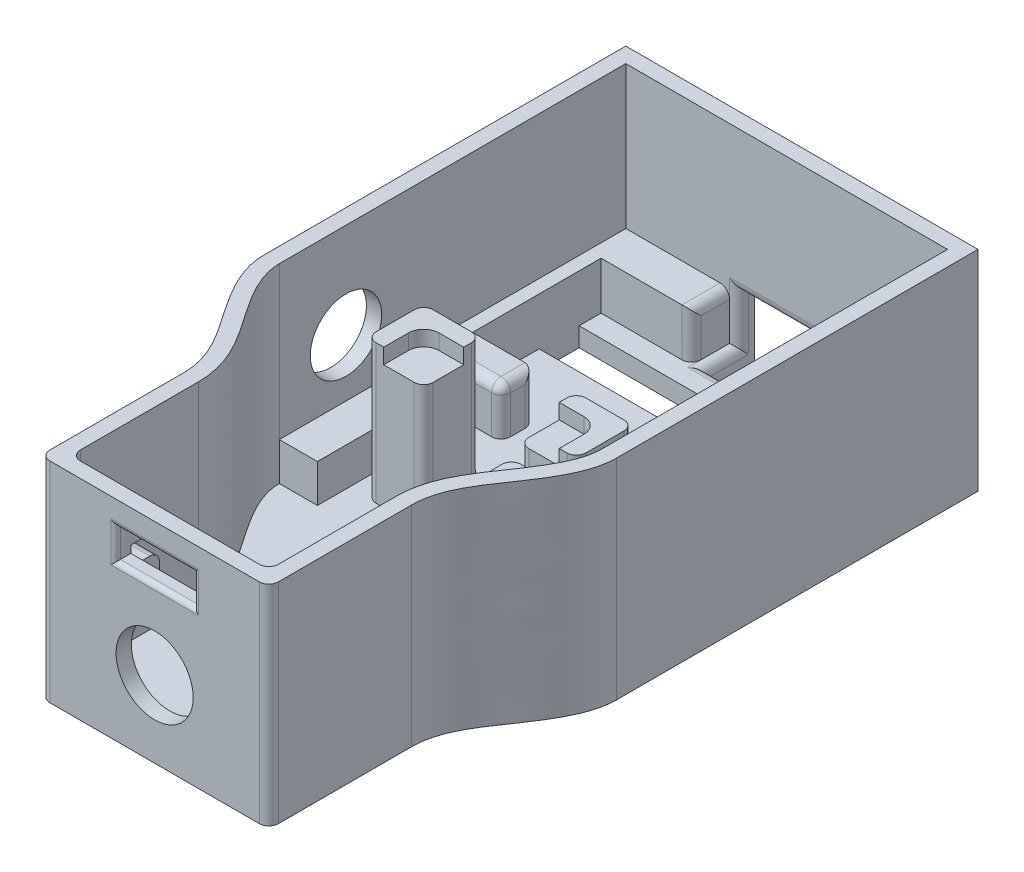
SolidWorks part; units mm, degrees
material "Melamine resin"
ref_plane "Front Plane" through (0, 0, 0) normal (0, 0, 1) x (1, 0, 0)
ref_plane "Top Plane" through (0, 0, 0) normal (0, 1, 0) x (1, 0, 0)
ref_plane "Right Plane" through (0, 0, 0) normal (1, 0, 0) x (0, 0, -1)
sketch "Sketch1" plane through (0, 0, 0) normal (0, 1, 0) x (1, 0, 0)
  line L0 (-18.5, 68) -> (0, 68)
  line L9 (0, 68) -> (0, 0)
  line L10 (-18.5, 68) -> (-18.5, 30)
  line L11 (0, 0) -> (-12, 0)
  line L12 (-12, 0) -> (-12, 15)
  line L13 (-18.5, 30) -> (-12, 30) construction
  line L14 (-12, 30) -> (-12, 15) construction
  line L15 (-15.25, 22.5) -> (-12, 22.5) construction
  line L16 (0, 1.6) -> (-10.4, 1.6)
  line L17 (-15.25, 30) -> (-15.25, 22.5) construction
  line L18 (-10.4, 1.6) -> (-10.4, 15)
  line L19 (-16.9, 66.4) -> (-16.9, 30)
  line L20 (-16.9, 66.4) -> (0, 66.4)
  line L21 (0, 68) -> (0, 66.4)
  line L22 (0, 1.6) -> (0, 0)
  spline S0 degree 3 poles (-18.5, 30) (-18.5, 27.3947) (-15.25, 22.3602) (-12, 17.8849) (-12, 15) knots 0 0 0 0 0.5 1 1 1 1
  spline S1 degree 1 poles (-16.9, 30) (-10.4, 15) knots 0 0 1 1 construction
  spline S2 degree 3 poles (-10.4, 15) (-10.4, 15.4256) (-10.4616, 16.2904) (-10.7983, 17.8861) (-11.54, 19.6983) (-12.6996, 21.6224) (-13.9392, 23.4086) (-15.1181, 25.1604) (-16.1016, 26.879) (-16.6415, 28.2398) (-16.8623, 29.268) (-16.9, 29.7529) (-16.9, 30) knots 0 0 0 0 0.0625 0.125 0.25 0.375 0.5 0.625 0.75 0.875 0.9375 1 1 1 1
  dimension "D1" = 18.5
  dimension "D2" = 68
  dimension "D3" = 15
  dimension "D4" = 15
  dimension "D5" = 12
  dimension "D6" = 1.6
extrude "Boss-Extrude1" add sketch "Sketch1" against normal blind 2 contours S0 L12 L11 L9 L0 L10
extrude "Boss-Extrude2" add sketch "Sketch1<3>" along normal blind 20 contours L18 S2 L19 L20 L9 L0 L10 S0 L12 L11 L16 region at (-9.25, 0, -67.2953)
sketch "Sketch1<3>" plane through (0, 0, 0) normal (0, 1, 0) x (1, 0, 0) same geometry as "Sketch1"
fillet "Fillet1" radius 1 2 edges at (-10.4, 10, -1.6) (-12, 9, 0)
mirror "Mirror1" about plane through (0, 0, 0) normal (1, 0, 0) of "Boss-Extrude2", "Fillet1", "Boss-Extrude1"
sketch "Sketch2" plane through (0, 0, 0) normal (0, 0, 1) x (1, 0, 0)
  line L0 (0, 0) -> (0, 6) construction
  line L1 (0, 6) -> (0, 15.84) construction
  line L2 (4.1, 14.24) -> (-4.1, 14.24)
  line L3 (4.1, 14.24) -> (4.1, 17.44)
  line L4 (4.1, 17.44) -> (-4.1, 17.44)
  line L5 (-4.1, 14.24) -> (-4.1, 17.44)
  line L6 (4.1, 14.24) -> (-4.1, 17.44) construction
  line L7 (4.1, 17.44) -> (-4.1, 14.24) construction
  line L8 (11, 20) -> (-11, 20) construction
  circle A0 centre (0, 6) radius 4.05
  point P4 (0, 15.84)
  dimension "D1" = 8.1
  dimension "D2" = 6
  dimension "D3" = 8.2
  dimension "D4" = 3.2
  dimension "D5" = 4.16
extrude "Cut-Extrude1" cut sketch "Sketch2" against normal up to next
sketch "Sketch3" plane through (0, 0, 0) normal (0, 1, 0) x (1, 0, 0)
  line L0 (-15.5, 55.65) -> (15.5, 55.65) construction
  line L1 (-16.9, 66.4) -> (-6, 66.4)
  line L2 (-16.9, 66.4) -> (-16.9, 45.4)
  line L3 (-16.9, 45.4) -> (-9, 45.4)
  line L4 (16.9, 66.4) -> (16.9, 45.4)
  line L5 (9, 45.4) -> (16.9, 45.4)
  line L7 (-9, 48.9) -> (-9, 45.4)
  line L9 (9, 48.9) -> (9, 45.4)
  line L10 (9, 48.9) -> (15.5, 48.9)
  line L11 (-15.5, 62.4) -> (-6, 62.4)
  line L12 (-15.5, 62.4) -> (-15.5, 48.9)
  line L13 (-15.5, 48.9) -> (-9, 48.9)
  line L14 (15.5, 62.4) -> (15.5, 48.9)
  line L15 (-9, 45.4) -> (9, 45.4) construction
  line L16 (-9, 48.9) -> (9, 48.9) construction
  line L17 (0, 66.4) -> (0, 62.4) construction
  line L18 (0, 62.4) -> (0, 48.9) construction
  line L19 (0, 48.9) -> (0, 45.4) construction
  line L20 (16.9, 66.4) -> (16.9, 30) construction
  line L21 (-6, 62.4) -> (-6, 66.4)
  line L22 (6, 62.4) -> (6, 66.4)
  line L23 (6, 62.4) -> (15.5, 62.4)
  line L24 (6, 66.4) -> (16.9, 66.4)
  line L25 (-6, 66.4) -> (6, 66.4) construction
  line L26 (-16.9, 66.4) -> (16.9, 66.4) construction
  line L27 (-6, 62.4) -> (6, 62.4) construction
  point P23 (0, 55.65)
  dimension "D1" = 31
  dimension "D2" = 13.5
  dimension "D3" = 12
  dimension "D4" = 4
  dimension "D5" = 18
  dimension "D6" = 3.5
extrude "Boss-Extrude3" add sketch "Sketch3" along normal blind 5
ref_plane "IR_mid" through (0, 0, -55.65) normal (0, 0, 1) x (1, 0, 0)
sketch "Sketch4" plane through (0, 0, -68) normal (0, 0, -1) x (-1, 0, 0)
  line L0 (18.5, -2) -> (-18.5, -2) construction
  line L1 (-5, -2) -> (5, -2)
  line L2 (-5, -2) -> (-5, 5)
  line L3 (-5, 5) -> (5, 5)
  line L4 (5, -2) -> (5, 5)
  line L5 (0, 5) -> (0, -2) construction
  dimension "D1" = 10
  dimension "D2" = 7
extrude "Cut-Extrude2" cut sketch "Sketch4" against normal blind 5
sketch "Sketch5" plane through (-18.5, 0, 0) normal (-1, 0, 0) x (0, 0, 1)
  line L0 (-37, 20) -> (-37, 0) construction
  line L1 (-68, 20) -> (-30, 20) construction
  line L2 (-37, 0) -> (0, 0) construction
  circle A0 centre (-37, 10) radius 3.75
  dimension "D1" = 7.5
  dimension "D2" = 37
extrude "Cut-Extrude3" cut sketch "Sketch5" against normal up to next
sketch "Sketch6" plane through (0, 0, 0) normal (0, 1, 0) x (1, 0, 0)
  line L0 (-16.9, 45.4) -> (-16.9, 30) construction
  line L1 (-16.9, 45.4) -> (-12.9, 45.4)
  line L2 (-16.9, 45.4) -> (-16.9, 30)
  line L3 (-16.9, 30) -> (-12.9, 30)
  line L4 (-12.9, 45.4) -> (-12.9, 30)
  spline S0 degree 3 poles (-10.4, 15) (-10.4, 15.4256) (-10.4616, 16.2904) (-10.7983, 17.8861) (-11.54, 19.6983) (-12.6996, 21.6224) (-13.9392, 23.4086) (-15.1181, 25.1604) (-16.1016, 26.879) (-16.6415, 28.2398) (-16.8623, 29.268) (-16.9, 29.7529) (-16.9, 30) knots 0 0 0 0 0.0625 0.125 0.25 0.375 0.5 0.625 0.75 0.875 0.9375 1 1 1 1 construction
  dimension "D1" = 4
extrude "Boss-Extrude4" add sketch "Sketch6" along normal blind 4
sketch "Sketch7" plane through (0, 0, -1.6) normal (0, 0, -1) x (-1, 0, 0)
  line L0 (4.1, 13) -> (9, 13)
  line L1 (11.1, 11) -> (4.1, 11)
  line L4 (4.1, 11) -> (4.1, 13)
  line L5 (9, 13) -> (9, 15)
  line L10 (4.1, 11) -> (0, 11) construction
  line L11 (9, 15) -> (4.1, 15)
  line L12 (-9.4, 0) -> (9.4, 0) construction
  line L13 (0, 0) -> (0, 11) construction
  line L14 (4.1, 15) -> (4.1, 17)
  line L15 (4.1, 17) -> (11.1, 17)
  line L16 (11.1, 11) -> (11.1, 17)
  line L17 (4.1, 13) -> (4.1, 15) construction
  dimension "D1" = 7
  dimension "D2" = 2
  dimension "D3" = 11
  dimension "D4" = 4.1
  dimension "D5" = 2
  dimension "D6" = 9
extrude "Boss-Extrude5" add sketch "Sketch7" along normal blind 3
sketch "Sketch9" plane through (0, 0, 0) normal (0, 1, 0) x (1, 0, 0)
  line L0 (0, 0) -> (0, 36.788) construction
  line L1 (-5.018, 33.288) -> (-11.018, 33.288)
  line L2 (-5.018, 33.288) -> (-5.018, 39.288)
  line L3 (-5.018, 39.288) -> (-11.018, 39.288)
  line L4 (-11.018, 33.288) -> (-11.018, 39.288)
  line L5 (-8.518, 36.788) -> (-8.518, 39.288) construction
  line L6 (-8.518, 36.788) -> (-11.018, 36.788) construction
  line L7 (0, 36.788) -> (-8.518, 36.788) construction
  point P0 (-8.518, 36.788)
  dimension "D1" = 2.5
  dimension "D2" = 2.5
  dimension "D3" = 8.518
  dimension "D4" = 36.788
  dimension "D5" = 6
  dimension "D6" = 6
extrude "Boss-Extrude7" add sketch "Sketch9" along normal up to surface (13 mm away) up to face at (-6.55, 13, -3.1)
sketch "Sketch10" plane through (0, 13, 0) normal (0, 1, 0) x (1, 0, 0)
  line L0 (-11.018, 39.288) -> (-11.018, 33.288)
  line L1 (-11.018, 33.288) -> (-11.018, 39.288) construction
  line L2 (-5.018, 33.288) -> (-11.018, 33.288) construction
  line L3 (-11.018, 33.288) -> (-9.218, 33.288)
  line L4 (-9.218, 33.288) -> (-9.218, 37.488) construction
  line L5 (-9.218, 37.488) -> (-5.018, 37.488) construction
  line L6 (-5.018, 39.288) -> (-5.018, 33.288) construction
  line L7 (-5.018, 37.488) -> (-5.018, 39.288)
  line L8 (-5.018, 39.288) -> (-11.018, 39.288)
  line L10 (-11.018, 39.288) -> (-5.018, 39.288) construction
  line L11 (-5.018, 37.488) -> (-7.618, 37.488)
  line L12 (-9.218, 33.288) -> (-9.218, 35.888)
  arc A0 (-9.218, 35.888) -> (-7.618, 37.488) centre (-7.618, 35.888) cw
  dimension "D2" = 1.6
  dimension "D1" = 1.8
extrude "Boss-Extrude8" add sketch "Sketch10" along normal blind 1.6
mirror "Mirror2" about plane through (0, 0, 0) normal (1, 0, 0) of "Boss-Extrude8", "Boss-Extrude5", "Boss-Extrude7"
sketch "Sketch11" plane through (0, 0, 0) normal (0, 1, 0) x (1, 0, 0)
  line L1 (5, 42.488) -> (-5, 42.488)
  line L2 (5, 42.488) -> (5, 37.488)
  line L3 (5, 37.488) -> (-5, 37.488)
  line L4 (-5, 42.488) -> (-5, 37.488)
  line L5 (5, 42.488) -> (-5, 37.488) construction
  line L6 (5, 37.488) -> (-5, 42.488) construction
  circle A0 centre (0, 39.988) radius 1.25 construction
  point P0 (0, 39.988)
  dimension "D1" = 10
  dimension "D2" = 5
extrude "Boss-Extrude9" add sketch "Sketch11" along normal blind 1.95
fillet "Fillet2" radius 1 28 edges at (-6, 2.5, -62.4) (-9, 2.5, -48.9) (-11.018, 7.3, -33.288) (-11.018, 7.3, -39.288) (-5, 0.975, -42.488) (-9, 2.5, -45.4) (0, 5, -66.4) (5, 2.5, -66.4) (-5, 2.5, -66.4) (-5, 0, -64.7) (5, 0, -64.7) (0, 0, -63) (6, 2.5, -62.4) (9, 2.5, -45.4) (9, 2.5, -48.9) (11.018, 7.3, -33.288) (11.018, 7.3, -39.288) (5, 0.975, -42.488) (5.018, 6.5, -33.288) (-5.018, 6.5, -33.288) (5.018, 7.3, -39.288) (-5.018, 7.3, -39.288) (6, 5, -64.4) (-6, 5, -64.4) (-9, 5, -47.15) (9, 5, -47.15) (-12.95, 5, -45.4) (12.95, 5, -45.4)
sketch "Sketch12" plane through (0, 1.95, 0) normal (0, 1, 0) x (1, 0, 0)
  circle A0 centre (0, 39.988) radius 1.7
  dimension "D1" = 3.4
extrude "Cut-Extrude4" cut sketch "Sketch12" against normal up to next
chamfer "Chamfer1" distance 1.8 angle 45 1 edges at (0, -2, -41.688)
fillet "Fillet3" radius 0.5 1 edges at (0, -0.2, -41.688)
chamfer "Chamfer2" distance 1.95 angle 45 6 edges at (0, 0, -37.488) (-5, 0, -39.488) (-4.7071, 0, -42.1951) (5, 0, -39.488) (4.7071, 0, -42.1951) (0, 0, -42.488)
fillet "Fillet4" radius 0.5 4 edges at (4.1, 15.84, 0) (0, 14.24, 0) (0, 17.44, 0) (-4.1, 15.84, 0)
fillet "Fillet5" radius 1 6 edges at (9, 14, -4.6) (6.55, 13, -4.6) (6.55, 15, -4.6) (-6.55, 13, -4.6) (-9, 14, -4.6) (-6.55, 15, -4.6)
sketch "Sketch13" plane through (0, 0, 0) normal (1, 0, 0) x (0, 0, -1)
  line L0 (68, -2) -> (30, -2) construction
  line L1 (55.9, -2) -> (60.1, -2)
  line L2 (55.9, -2) -> (55.9, 0)
  line L3 (55.9, 0) -> (60.1, 0)
  line L4 (60.1, -2) -> (60.1, 0)
  line L5 (48.9, 0) -> (62.4, 0) construction
  line L6 (68, -2) -> (68, 5) construction
  point P8 (58, -2)
  dimension "D1" = 10
  dimension "D2" = 4.2
extrude "Cut-Extrude5" cut sketch "Sketch13" against normal up to surface and the other way up to surface up to face at (-15.5, 2.5, -55.65) other way up to face at (15.5, 2.5, -55.65)
ref_plane "suspension_plate" through (0, 0, -58) normal (0, 0, -1) x (-1, 0, 0)
